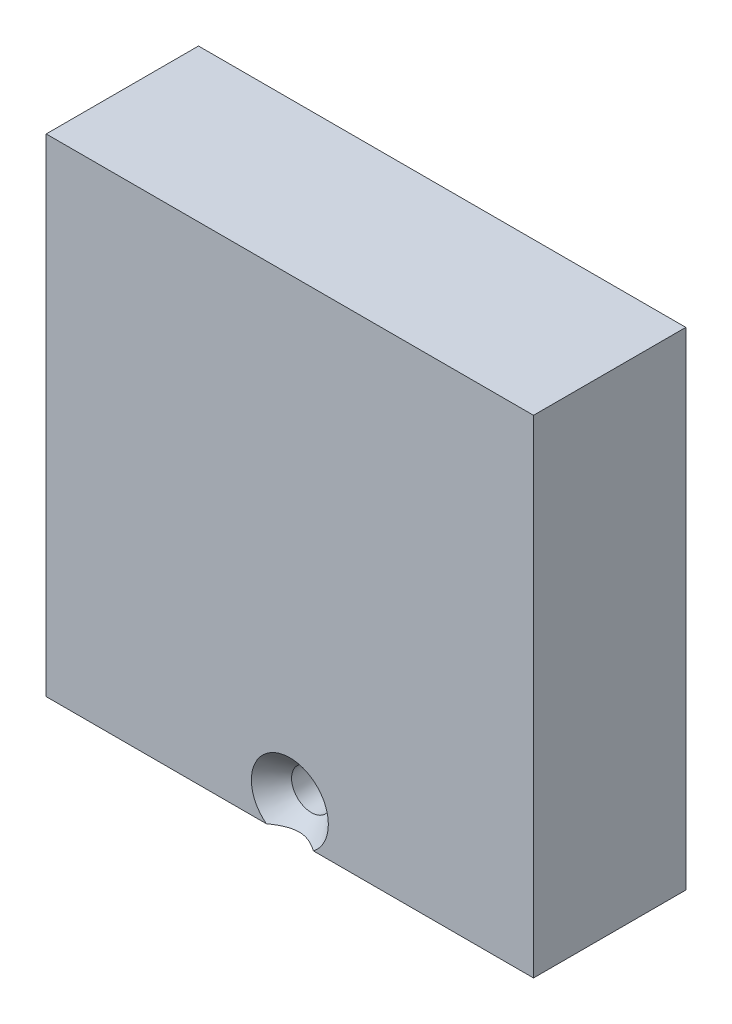
SolidWorks part; units mm, degrees
ref_plane "Plan de face" through (0, 0, 0) normal (0, 0, 1) x (1, 0, 0)
ref_plane "Plan de dessus" through (0, 0, 0) normal (0, 1, 0) x (1, 0, 0)
ref_plane "Plan de droite" through (0, 0, 0) normal (1, 0, 0) x (0, 0, -1)
sketch "Esquisse1" plane through (0, 0, 0) normal (0, 0, 1) x (1, 0, 0)
  line L1 (0, 0) -> (32, 0)
  line L2 (0, 0) -> (0, 32)
  line L3 (0, 32) -> (32, 32)
  line L4 (32, 0) -> (32, 32)
  dimension "D1" = 32
  dimension "D2" = 32
extrude "Boss.-Extru.1" add sketch "Esquisse1" along normal blind 10
sketch "Esquisse2" plane through (0, 0, 0) normal (0, -1, 0) x (1, 0, 0)
  line L0 (3.75, 0) -> (3.75, 3.4)
  line L1 (0, 0) -> (32, 0) construction
  line L2 (3.75, 3.4) -> (4.25, 3.4)
  line L3 (4.25, 3.4) -> (4.25, 4.2)
  line L4 (4.25, 4.2) -> (3.75, 4.2)
  line L5 (3.75, 4.2) -> (3.75, 7)
  line L6 (3.75, 7) -> (28.25, 7)
  line L7 (28.25, 7) -> (28.25, 4.2)
  line L8 (28.25, 4.2) -> (27.75, 4.2)
  line L9 (27.75, 4.2) -> (27.75, 3.4)
  line L10 (27.75, 3.4) -> (28.25, 3.4)
  line L11 (28.25, 3.4) -> (28.25, 0)
  line L12 (28.25, 0) -> (3.75, 0)
  line L13 (0, 10) -> (32, 10) construction
  point P13 (16, 0)
  point P15 (16, 8)
  point P18 (16, 10)
  dimension "D1" = 24.5
  dimension "D2" = 0.5
  dimension "D3" = 0.8
  dimension "D4" = 2.8
  dimension "D5" = 7
extrude "Enlèv. mat.-Extru.1" cut sketch "Esquisse2" against normal blind 28.5
sketch "Esquisse4" plane through (0, 0, 7) normal (0, 0, -1) x (-1, 0, 0)
  line L3 (-28.25, 28.5) -> (-28.25, 0) construction
  line L4 (-3.75, 28.5) -> (-3.75, 0) construction
  line L5 (-28.25, 15.5) -> (-28.25, 28.5)
  line L6 (-28.25, 28.5) -> (-3.75, 28.5)
  line L7 (-3.75, 28.5) -> (-3.75, 15.5)
  line L8 (-3.75, 28.5) -> (-28.25, 28.5) construction
  arc A0 (-28.25, 15.5) -> (-3.75, 15.5) centre (-16, 15.5) cw
  dimension "D1" = 12.25
  dimension "D2" = 13
extrude "Boss.-Extru.2" add sketch "Esquisse4" along normal up to surface (7 mm away) up to face at (16, 15.125, 0)
sketch "Esquisse5" plane through (0, 0, 3.4) normal (0, 0, -1) x (-1, 0, 0)
  line L0 (-4.25, 15.5) -> (0, 15.5)
  line L1 (0, 15.5) -> (0, 32)
  line L2 (0, 32) -> (-32, 32)
  line L3 (-32, 32) -> (-32, 15.5)
  line L4 (-32, 15.5) -> (-27.75, 15.5)
  line L5 (-32, 0) -> (-32, 32) construction
  line L6 (0, 32) -> (0, 0) construction
  line L7 (-32, 32) -> (0, 32) construction
  line L8 (-27.75, 18.9641) -> (-27.75, 0) construction
  arc A0 (-27.75, 15.5) -> (-4.25, 15.5) centre (-16, 15.5) cw
  arc A3 (-3.75, 15.5) -> (-28.25, 15.5) centre (-16, 15.5) ccw construction
  dimension "D1" = 11.75
extrude "Boss.-Extru.3" add sketch "Esquisse5" against normal up to surface (0.8 mm away) up to face at (28.0311, 8.6205, 4.2)
sketch "Esquisse10" plane through (0, 0, 10) normal (0, 0, 1) x (1, 0, 0)
  line L0 (0, 0) -> (32, 0) construction
  point P0 (16, 2)
  point P4 (16, 0)
  dimension "D1" = 2
hole_wizard "Fraisage pour vis à tête fraisée bombée #33" positions "Esquisse11" profile "Esquisse12" countersink size "#3" standard "Ansi Inch" end condition through all
sketch "Esquisse11" plane through (0, 0, 10) normal (0, 0, 1) x (1, 0, 0)
  point P0 (16, 2)
sketch "Esquisse12" plane through (16, 2, 10) normal (1, 0, 0) x (0, -1, 0)
  line L0 (0, 0) -> (0, 10)
  line L1 (0, 10) -> (1.3, 10)
  line L2 (1.3, 10) -> (1.3, 1.4119)
  line L3 (1.3, 1.4119) -> (2.5273, 0)
  line L5 (2.5273, 0) -> (0, 0)
  line L6 (-1.3, 1.4119) -> (-2.5273, 0) construction
  line L11 (0, -6.35) -> (0, 107.95) construction
  dimension "Diamètre du perçage jusqu'au prochain" = 2.6
  dimension "Profondeur du perçage jusqu'au prochain" = 10
  dimension "Diamètre du fraisage entrant" = 5.0546
  dimension "Angle du fraisage entrant" = 82
